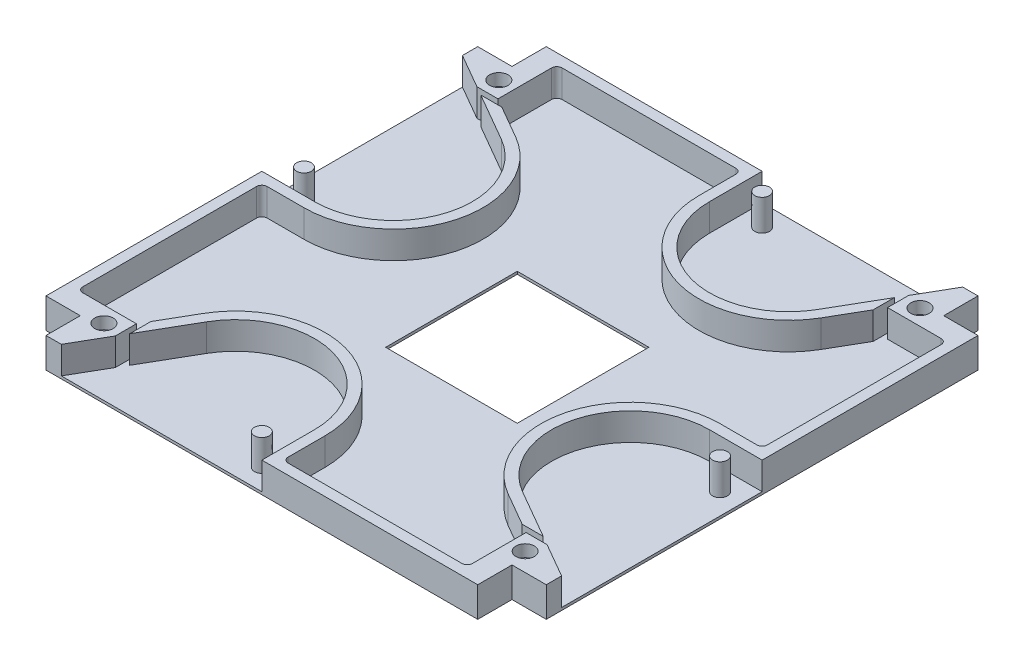
SolidWorks part; units mm, degrees
material "7075-T6 (SN)"
ref_plane "Front Plane" through (0, 0, 0) normal (0, 0, 1) x (1, 0, 0)
ref_plane "Top Plane" through (0, 0, 0) normal (0, 1, 0) x (1, 0, 0)
ref_plane "Right Plane" through (0, 0, 0) normal (1, 0, 0) x (0, 0, -1)
sketch "Sketch1" plane through (0, 0, 0) normal (0, 1, 0) x (1, 0, 0)
  line L0 (0, 0) -> (0, 6.51)
  line L21 (0, 6.51) -> (82, 6.51)
  line L22 (82, 6.51) -> (82, 0)
  line L23 (82, 0) -> (88.51, 0)
  line L24 (88.51, 0) -> (88.51, -82)
  line L25 (88.51, -82) -> (82, -82)
  line L26 (82, -82) -> (82, -88.51)
  line L27 (82, -88.51) -> (0, -88.51)
  line L28 (0, -88.51) -> (0, -82)
  line L29 (0, -82) -> (-6.51, -82)
  line L30 (-6.51, -82) -> (-6.51, 0)
  line L31 (-6.51, 0) -> (0, 0)
  dimension "D1" = 82
  dimension "D2" = 6.51
extrude "Boss-Extrude1" add sketch "Sketch1" along normal blind 0.5
sketch "Sketch2" plane through (0, 0.5, 0) normal (0, 1, 0) x (1, 0, 0)
  line L0 (-6.51, 0) -> (-6.51, -82) construction
  line L1 (0, 6.51) -> (41, 6.51)
  line L2 (0, 6.51) -> (0, 4.51)
  line L3 (0, 4.51) -> (41, 4.51)
  line L4 (41, 6.51) -> (41, 4.51)
  line L5 (88.51, 0) -> (86.51, 0)
  line L6 (88.51, 0) -> (88.51, -41)
  line L7 (88.51, -41) -> (86.51, -41)
  line L8 (86.51, 0) -> (86.51, -41)
  line L9 (82, -88.51) -> (41, -88.51)
  line L10 (82, -88.51) -> (82, -86.51)
  line L11 (82, -86.51) -> (41, -86.51)
  line L12 (41, -88.51) -> (41, -86.51)
  line L13 (-6.51, -82) -> (-4.51, -82)
  line L14 (-6.51, -82) -> (-6.51, -41)
  line L15 (-6.51, -41) -> (-4.51, -41)
  line L16 (-4.51, -82) -> (-4.51, -41)
  line L17 (-6.51, -82) -> (0, -82) construction
  line L18 (41, -3.49) -> (41, 28.4809) construction
  line L19 (56, 11.51) -> (70.2074, 11.51) construction
  line L20 (82, 6.51) -> (0, 6.51) construction
  line L21 (68.9904, -10.99) -> (79.094, 6.51)
  line L22 (79.094, 6.51) -> (82, 6.51)
  line L23 (82, 6.51) -> (82, 0)
  line L24 (82, 0) -> (86.51, 0)
  line L25 (41, 4.51) -> (41, -3.49)
  line L26 (86.51, -4) -> (75.3355, -4)
  line L27 (39, 4.51) -> (39, -3.49)
  line L28 (72.3908, -8) -> (73.0261, -8)
  line L29 (73.0261, -8) -> (70.7224, -11.99)
  line L30 (73.0261, -8) -> (75.3355, -4)
  line L31 (75.3355, -4) -> (75.3355, 0)
  line L32 (74.3355, -1.7321) -> (74.3355, -5.7321)
  circle A0 centre (56, -3.49) radius 15
  circle A1 centre (56, -3.49) radius 17 construction
  arc A2 (70.7224, -11.99) -> (39, -3.49) centre (56, -3.49) cw
  line M24 (88.51, -82) -> (88.51, 0)
  line M25 (88.51, 0) -> (82, 0)
  line M26 (82, 0) -> (82, 6.51)
  line M27 (82, 6.51) -> (0, 6.51)
  line M28 (0, 6.51) -> (0, 0)
  dimension "D3" = 30
  dimension "D6" = 34
  dimension "D1" = 41
  dimension "D2" = 2
  dimension "D4" = 30
  dimension "D7" = 4
  dimension "D8" = 4
  dimension "D5" = 5
  dimension "D9" = 1
extrude "Boss-Extrude2" add sketch "Sketch2" along normal blind 5.2 contours L4 L3 M27 M28 | A2 L29 L28 L21 A0 L25 L3 L27 | L8 L7 M25 M24 | L26 L8 L21 M25 M26 M27 region at (20.5, 0.5, -5.51) region at (40.5671, 0.5, -0.51) region at (80.332, 0.5, 0.0167) region at (87.51, 0.5, 20.5)
sketch "Sketch3" [suppressed] plane through (0, 0.5, 0) normal (0, 1, 0) x (1, 0, 0)
  line L0 (35.5217, -6.4679) -> (39.51, -26.4679)
  line L1 (39.51, -26.4679) -> (39.51, -29.4679)
  line L2 (39.51, -29.4679) -> (79.51, -29.4679)
  line L3 (79.51, -29.4679) -> (79.51, -26.4679)
  line L4 (79.51, -26.4679) -> (83.4983, -6.4679)
  line L6 (35.5217, -6.4679) -> (39.5217, -6.4679)
  line L7 (83.4983, -6.4679) -> (79.4983, -6.4679)
  line L9 (89.51, -41) -> (89.51, 0) construction
  arc A0 (79.4983, -6.4679) -> (39.5217, -6.4679) centre (59.51, -5.7836) cw
  circle A1 centre (58.485, 0) radius 15 construction
  dimension "D3" = 20
  dimension "D7" = 30
  dimension "D1" = 3
  dimension "D2" = 4
  dimension "D4" = 20
  dimension "D5" = 40
  dimension "D6" = 10
extrude "Boss-Extrude3" [suppressed] add sketch "Sketch3" along normal blind 6
ref_plane "Plane1" through (41, 0, 41) normal (0.7071, 0, 0.7071) x (0.7071, 0, -0.7071)
ref_plane "Plane2" through (0, 0, 0) normal (0.7071, 0, -0.7071) x (-0.7071, 0, -0.7071)
ref_axis "Axis1" through (41, -0.325, 41) along (0, 1, 0)
pattern_circular "CirPattern1" count 4 every 90 about axis through (41, -0.325, 41) along (0, 1, 0) of "Boss-Extrude2"
sketch "Sketch4" plane through (0, 0, 0) normal (0, -1, 0) x (1, 0, 0)
  line L0 (78, -6.51) -> (78, -0.51) construction
  line L1 (82, -6.51) -> (0, -6.51) construction
  line L2 (82, 0) -> (82, -6.51) construction
  line L3 (88.51, 78) -> (82.51, 78) construction
  line L4 (88.51, 82) -> (88.51, 0) construction
  line L5 (4, 88.51) -> (4, 82.51) construction
  line L6 (0, 88.51) -> (82, 88.51) construction
  line L7 (-6.51, 4) -> (-0.51, 4) construction
  line L8 (-6.51, 0) -> (-6.51, 82) construction
  line L10 (82, 82) -> (88.51, 82) construction
  line L11 (0, 82) -> (0, 88.51) construction
  line L12 (0, 0) -> (-6.51, 0) construction
  point P7 (78, -0.51)
  dimension "D1" = 6
  dimension "D2" = 4
  dimension "D3" = 4
  dimension "D4" = 4
  dimension "D5" = 4
  dimension "D6" = 6
  dimension "D7" = 6
  dimension "D8" = 6
sketch "Sketch8" plane through (0, 0.5, 0) normal (0, 1, 0) x (1, 0, 0)
  line L0 (2.906, -88.51) -> (41, -88.51) construction
  line L1 (41, -88.51) -> (41, -78.51) construction
  circle A0 centre (37, -84.51) radius 1.4
  dimension "D1" = 2.8
  dimension "D2" = 4
  dimension "D3" = 4
extrude "Boss-Extrude4" add sketch "Sketch8" along normal blind 5.9
pattern_circular "CirPattern2" count 4 every 90 about axis through (41, -0.325, 41) along (0, 1, 0) of "Boss-Extrude4"
fillet "Fillet1" radius 1 8 edges at (-4.51, 3.1, 78) (-4.51, 3.1, 43) (4, 3.1, -4.51) (39, 3.1, -4.51) (86.51, 3.1, 4) (86.51, 3.1, 39) (78, 3.1, 86.51) (43, 3.1, 86.51)
sketch "Sketch11" plane through (0, 0.5, 0) normal (0, 1, 0) x (1, 0, 0)
  line L0 (54, -53) -> (54, -28)
  line L1 (54, -28) -> (29, -28)
  line L2 (29, -28) -> (29, -53)
  line L3 (29, -53) -> (54, -53)
  dimension "D1" = 25
  dimension "D2" = 25
  dimension "D3" = 29
  dimension "D4" = 29
extrude "Cut-Extrude2" cut sketch "Sketch11" against normal through all
sketch "Sketch12" plane through (0, 0.5, 0) normal (0, 1, 0) x (1, 0, 0)
  line L0 (0, 0) -> (-6.51, 0) construction
  line L2 (82, -88.51) -> (82, -82) construction
  point P0 (40.5, -41.5)
  dimension "D1" = 41.5
  dimension "D2" = 41.5
sketch "Sketch14" plane through (0, 6.4, 0) normal (0, 1, 0) x (1, 0, 0)
  point P0 (37, -84.51)
sketch "Sketch15" plane through (0, 5.7, 0) normal (0, 1, 0) x (1, 0, 0)
  line L0 (82, -82) -> (88.51, -82) construction
  line L2 (78, -85.51) -> (78, -75.3355) construction
  circle A0 centre (81, -78.5) radius 0.9
  circle A1 centre (78.5, -1) radius 0.9
  circle A2 centre (1, -3.5) radius 0.9
  circle A3 centre (3.5, -81) radius 0.9
  point P0 (1, -3.5)
  point P1 (1, -3.5)
  point P2 (3.5, -81)
  point P3 (81, -78.5)
  point P4 (78.5, -1)
  point P5 (3.5, -81)
  point P12 (0, 0)
  point P13 (0, 0)
  point P14 (0, 0)
  point P15 (0, 0)
  point P16 (0, 0)
  point P17 (0, 0)
  dimension "D3" = 1.8
  dimension "D4" = 1.8
  dimension "D5" = 1.8
  dimension "D6" = 1.8
  dimension "D1" = 3.5
  dimension "D2" = 3
extrude "Cut-Extrude3" cut sketch "Sketch15" against normal through all
sketch "Sketch16" plane through (0, 5.7, 0) normal (0, 1, 0) x (1, 0, 0)
  circle A0 centre (78.5, -1) radius 1.75
  circle A1 centre (81, -78.5) radius 1.75
  circle A2 centre (3.5, -81) radius 1.75
  circle A3 centre (1, -3.5) radius 1.75
  point P12 (0, 0)
  point P13 (0, 0)
  point P14 (0, 0)
  dimension "D1" = 3.5
  dimension "D2" = 3.5
  dimension "D3" = 3.5
  dimension "D4" = 3.5
extrude "Cut-Extrude4" cut sketch "Sketch16" against normal blind 2.3
hole_wizard "CBORE for M1.6 SHCS2" positions "3DSketch2" profile "Sketch18" counterbore size "M1.6" standard "ANSI Metric" end condition through all
sketch3d "3DSketch2"
  line L0 (81, 0, 78.5) -> (81, 3.4, 78.5) construction
  line L1 (78.5, 0, 1) -> (78.5, 3.4, 1) construction
  line L2 (1, 0, 3.5) -> (1, 3.4, 3.5) construction
  line L3 (3.5, 0, 81) -> (3.5, 3.4, 81) construction
  point P0 (81, 0, 78.5)
  point P4 (78.5, 0, 1)
  point P8 (1, 0, 3.5)
  point P12 (3.5, 0, 81)
sketch "Sketch18" plane through (81, 0, 78.5) normal (1, 0, 0) x (0, 0, -1)
  line L0 (0, 0) -> (0, 6.4)
  line L1 (0, 6.4) -> (0.9, 6.4)
  line L3 (0.9, 6.4) -> (0.9, 1.6)
  line L4 (0.9, 1.6) -> (1.75, 1.6)
  line L5 (1.75, 1.6) -> (1.75, 0)
  line L7 (1.75, 0) -> (0, 0)
  line L11 (0, -6.35) -> (0, 107.95) construction
  dimension "Thru Hole Dia." = 1.8
  dimension "Thru Hole Depth" = 6.4
  dimension "C'Bore Dia." = 3.5
  dimension "C'Bore Depth" = 1.6
equation "\"D6@Sketch2\"=\"D3@Sketch2\"+4"
equation "\"D3@Sketch4\"=\"D2@Sketch4\""
equation "\"D4@Sketch4\"=\"D3@Sketch4\""
equation "\"D5@Sketch4\"=\"D4@Sketch4\""
equation "\"D6@Sketch4\"=\"D1@Sketch4\""
equation "\"D7@Sketch4\"=\"D6@Sketch4\""
equation "\"D8@Sketch4\"=\"D7@Sketch4\""
